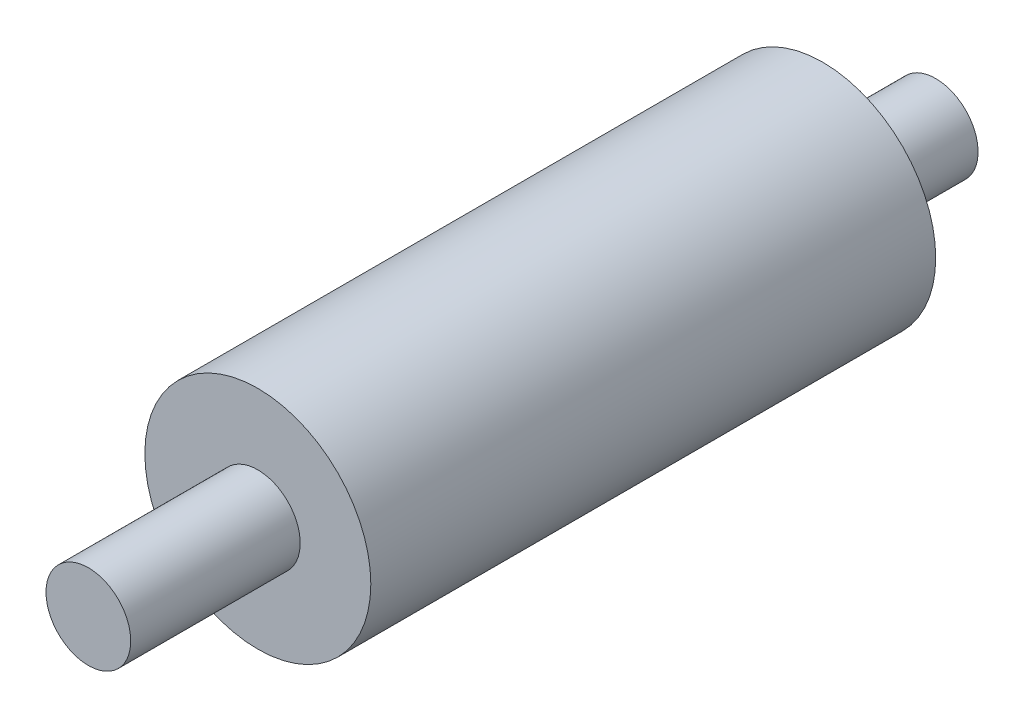
SolidWorks part; units mm, degrees
ref_plane "Front Plane" through (0, 0, 0) normal (0, 0, 1) x (1, 0, 0)
ref_plane "Top Plane" through (0, 0, 0) normal (0, 1, 0) x (1, 0, 0)
ref_plane "Right Plane" through (0, 0, 0) normal (1, 0, 0) x (0, 0, -1)
sketch "Sketch1" plane through (0, 0, 0) normal (0, 0, 1) x (1, 0, 0)
  circle A0 centre (0, 0) radius 20
  dimension "D1" = 40
extrude "Boss-Extrude1" add sketch "Sketch1" along normal blind 100
sketch "Sketch2" plane through (0, 0, 100) normal (0, 0, 1) x (1, 0, 0)
  circle A0 centre (0, 0) radius 7.5
  dimension "D1" = 15
extrude "Boss-Extrude2" add sketch "Sketch2" along normal blind 30
pattern_linear "LPattern1" count 2 spacing 130 along (0, 0, -1) of "Boss-Extrude2"
sketch "Sketch3" plane through (0, 0, -30) normal (0, 0, -1) x (-1, 0, 0)
  circle A0 centre (0, 0) radius 7.5
extrude "Cut-Extrude1" cut sketch "Sketch3" against normal blind 10
